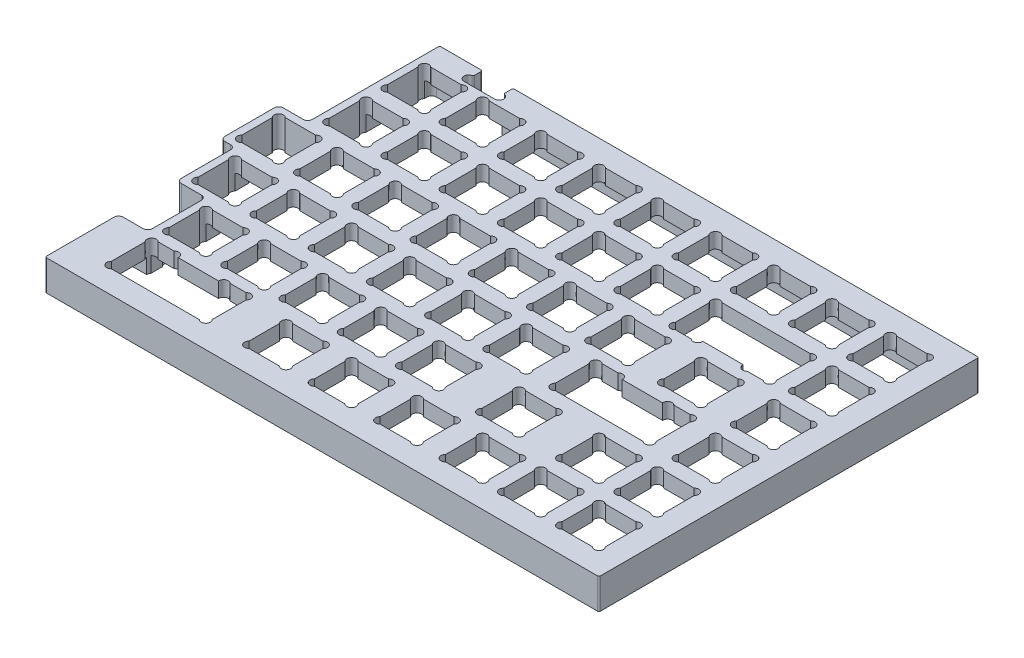
SolidWorks part; units mm, degrees
material "6061-T6 (SS)"
ref_plane "Front Plane" through (0, 0, 0) normal (0, 0, 1) x (1, 0, 0)
ref_plane "Top Plane" through (0, 0, 0) normal (0, 1, 0) x (1, 0, 0)
ref_plane "Right Plane" through (0, 0, 0) normal (1, 0, 0) x (0, 0, -1)
sketch "Sketch1" plane through (0, 0, 0) normal (0, 1, 0) x (1, 0, 0)
  line L0 (0, 0) -> (0, 124.3)
  line L1 (0, 124.3) -> (-176.45, 124.3)
  line L2 (-176.45, 124.3) -> (-176.45, 81.2)
  line L3 (-176.45, 81.2) -> (-185.975, 81.2)
  line L4 (-185.975, 81.2) -> (-185.975, 62.15)
  line L5 (-185.975, 62.15) -> (-181.2125, 62.15)
  line L6 (-181.2125, 62.15) -> (-181.2125, 43.1)
  line L7 (-181.2125, 43.1) -> (-171.6875, 43.1)
  line L8 (-171.6875, 43.1) -> (-171.6875, 24.05)
  line L9 (-171.6875, 24.05) -> (-181.2125, 24.05)
  line L10 (-181.2125, 24.05) -> (-181.2125, 0)
  line L11 (-181.2125, 0) -> (0, 0)
  dimension "D2" = 19.05
  dimension "D3" = 4.7625
  dimension "D4" = 9.525
  dimension "D6" = 176.45
  dimension "D7" = 9.525
  dimension "D5" = 43.1
  dimension "D1" = 24.05
extrude "Plate Frame" add sketch "Sketch1" along normal blind 5
sketch "Sketch2" plane through (0, 5, 0) normal (0, 1, 0) x (1, 0, 0)
  line L0 (-52.625, 14.525) -> (-33.575, 14.525) construction
  line L1 (-33.575, 14.525) -> (-14.525, 14.525) construction
  line L2 (-14.525, 14.525) -> (-14.525, 33.575) construction
  line L3 (-14.525, 33.575) -> (-14.525, 52.625) construction
  line L4 (-14.525, 52.625) -> (-14.525, 71.675) construction
  line L5 (-14.525, 71.675) -> (-14.525, 90.725) construction
  line L6 (-14.525, 90.725) -> (-14.525, 109.775) construction
  line L7 (-14.525, 109.775) -> (-33.575, 109.775) construction
  line L8 (-33.575, 109.775) -> (-52.625, 109.775) construction
  line L9 (-52.625, 109.775) -> (-71.675, 109.775) construction
  line L10 (-71.675, 109.775) -> (-90.725, 109.775) construction
  line L11 (-90.725, 109.775) -> (-109.775, 109.775) construction
  line L12 (-109.775, 109.775) -> (-128.825, 109.775) construction
  line L13 (-128.825, 109.775) -> (-147.875, 109.775) construction
  line L14 (-147.875, 109.775) -> (-166.925, 109.775) construction
  line L15 (-33.575, 33.575) -> (-14.525, 33.575) construction
  line L16 (-33.575, 33.575) -> (-33.575, 14.525) construction
  line L17 (-166.925, 90.725) -> (-147.875, 90.725) construction
  line L18 (-147.875, 90.725) -> (-128.825, 90.725) construction
  line L19 (-128.825, 90.725) -> (-109.775, 90.725) construction
  line L20 (-109.775, 90.725) -> (-90.725, 90.725) construction
  line L21 (-90.725, 90.725) -> (-71.675, 90.725) construction
  line L22 (-166.925, 90.725) -> (-166.925, 109.775) construction
  line L23 (-176.45, 124.3) -> (-176.45, 81.2) construction
  line L24 (-176.45, 71.675) -> (-157.4, 71.675) construction
  line L25 (-157.4, 71.675) -> (-138.35, 71.675) construction
  line L26 (-138.35, 71.675) -> (-119.3, 71.675) construction
  line L27 (-119.3, 71.675) -> (-100.25, 71.675) construction
  line L28 (-100.25, 71.675) -> (-81.2, 71.675) construction
  line L29 (-81.2, 71.675) -> (-62.15, 71.675) construction
  line L30 (-171.6875, 52.625) -> (-152.6375, 52.625) construction
  line L31 (-185.975, 81.2) -> (-185.975, 62.15) construction
  line L32 (-152.6375, 52.625) -> (-133.5875, 52.625) construction
  line L33 (-133.5875, 52.625) -> (-114.5375, 52.625) construction
  line L34 (-114.5375, 52.625) -> (-95.4875, 52.625) construction
  line L35 (-95.4875, 52.625) -> (-76.4375, 52.625) construction
  line L36 (-162.1625, 33.575) -> (-143.1125, 33.575) construction
  line L37 (-143.1125, 33.575) -> (-124.0625, 33.575) construction
  line L38 (-124.0625, 33.575) -> (-105.0125, 33.575) construction
  line L39 (-105.0125, 33.575) -> (-85.9625, 33.575) construction
  line L41 (-59.7687, 33.575) -> (-33.575, 33.575) construction
  line L42 (-52.625, 14.525) -> (-74.0562, 14.525) construction
  line L43 (-74.0562, 14.525) -> (-95.4875, 14.525) construction
  line L44 (-95.4875, 14.525) -> (-116.9187, 14.525) construction
  line L45 (-38.3375, 71.675) -> (-14.525, 71.675) construction
  point P0 (-14.525, 14.525)
  point P1 (-14.525, 33.575)
  point P2 (-14.525, 52.625)
  point P3 (-14.525, 71.675)
  point P4 (-14.525, 90.725)
  point P5 (-14.525, 109.775)
  point P6 (-33.575, 14.525)
  point P7 (-52.625, 14.525)
  point P8 (-33.575, 33.575)
  point P9 (-33.575, 109.775)
  point P10 (-52.625, 109.775)
  point P11 (-71.675, 109.775)
  point P12 (-90.725, 109.775)
  point P13 (-109.775, 109.775)
  point P14 (-128.825, 109.775)
  point P15 (-147.875, 109.775)
  point P16 (-166.925, 109.775)
  point P34 (-166.925, 90.725)
  point P35 (-147.875, 90.725)
  point P36 (-128.825, 90.725)
  point P37 (-109.775, 90.725)
  point P38 (-90.725, 90.725)
  point P39 (-71.675, 90.725)
  point P48 (-176.45, 71.675)
  point P49 (-157.4, 71.675)
  point P50 (-138.35, 71.675)
  point P51 (-119.3, 71.675)
  point P52 (-100.25, 71.675)
  point P53 (-81.2, 71.675)
  point P54 (-62.15, 71.675)
  point P62 (-152.6375, 52.625)
  point P65 (-185.975, 71.675)
  point P66 (-171.6875, 52.625)
  point P67 (-133.5875, 52.625)
  point P68 (-114.5375, 52.625)
  point P69 (-95.4875, 52.625)
  point P70 (-76.4375, 52.625)
  point P77 (-143.1125, 33.575)
  point P78 (-162.1625, 33.575)
  point P79 (-124.0625, 33.575)
  point P80 (-105.0125, 33.575)
  point P81 (-85.9625, 33.575)
  point P87 (-74.0562, 14.525)
  point P89 (-95.4875, 14.525)
  point P90 (-116.9187, 14.525)
  point P91 (-59.7687, 33.575)
  point P95 (-38.3375, 71.675)
  dimension "D1" = 19.05
  dimension "D2" = 9.525
  dimension "D3" = 9.525
  dimension "D4" = 4.7625
  dimension "D5" = 9.525
  dimension "D6" = 26.1938
  dimension "D7" = 21.4313
  dimension "D8" = 23.8125
sketch "Sketch3" plane through (0, 5, 0) normal (0, 1, 0) x (1, 0, 0)
  line L5 (-21.625, 19.5037) -> (-21.625, 9.5463)
  line L6 (-21.625, 21.625) -> (-7.425, 21.625) construction
  line L7 (-21.625, 21.625) -> (-21.625, 7.425) construction
  line L8 (-21.625, 7.425) -> (-7.425, 7.425) construction
  line L9 (-7.425, 21.625) -> (-7.425, 7.425) construction
  line L10 (-21.625, 21.625) -> (-7.425, 7.425) construction
  line L11 (-21.625, 7.425) -> (-7.425, 21.625) construction
  line L12 (-19.5037, 7.425) -> (-9.5463, 7.425)
  line L13 (-7.425, 19.5037) -> (-7.425, 9.5463)
  line L14 (-19.5037, 21.625) -> (-9.5463, 21.625)
  arc A4 (-21.625, 19.5037) -> (-19.5037, 21.625) centre (-20.5643, 20.5643) cw
  arc A5 (-7.425, 19.5037) -> (-9.5463, 21.625) centre (-8.4857, 20.5643) ccw
  arc A6 (-7.425, 9.5463) -> (-9.5463, 7.425) centre (-8.4857, 8.4857) cw
  arc A7 (-19.5037, 7.425) -> (-21.625, 9.5463) centre (-20.5643, 8.4857) cw
  point P13 (-14.525, 14.525)
  dimension "D1" = 1.5
  dimension "D2" = 14.2
extrude "1U" cut sketch "Sketch3" against normal through all
pattern_sketch "Sketch-Pattern1" of "1U" driven by "Sketch2"
sketch "Sketch5" plane through (0, 5, 0) normal (0, 1, 0) x (1, 0, 0)
  line L0 (-14.525, 90.725) -> (-43.1, 90.725) construction
  line L1 (-14.525, 52.625) -> (-45.4812, 52.625) construction
  line L2 (-116.9187, 14.525) -> (-152.6375, 14.525) construction
  point P0 (-43.1, 90.725)
  point P1 (-45.4812, 52.625)
  point P2 (-152.6375, 14.525)
  dimension "D1" = 28.575
  dimension "D2" = 30.9563
  dimension "D3" = 35.7188
sketch "Sketch4" plane through (0, 5, 0) normal (0, 1, 0) x (1, 0, 0)
  line L10 (-59.6, 97.775) -> (-51.95, 90.125) construction
  line L11 (-59.6, 82.475) -> (-50.15, 82.475) construction
  line L12 (-50.15, 83.675) -> (-36.05, 83.675) construction
  line L13 (-36.05, 82.475) -> (-26.6, 82.475) construction
  line L14 (-59.6, 82.475) -> (-51.95, 90.125) construction
  line L15 (-59.6, 97.775) -> (-26.6, 97.775) construction
  line L16 (-26.6, 97.775) -> (-26.6, 82.475) construction
  line L17 (-26.6, 97.775) -> (-34.25, 90.125) construction
  line L18 (-59.6, 82.475) -> (-59.6, 97.775) construction
  line L19 (-50.15, 83.675) -> (-50.15, 82.475) construction
  line L20 (-36.05, 83.675) -> (-36.05, 82.475) construction
  line L21 (-36.05, 83.675) -> (-50.15, 97.775) construction
  line L22 (-34.25, 90.125) -> (-26.6, 82.475) construction
  line L23 (-36.05, 82.475) -> (-31.325, 87.2) construction
  line L24 (-50.15, 82.475) -> (-54.875, 87.2) construction
  line L25 (-57.4787, 97.775) -> (-28.7213, 97.775)
  line L26 (-26.6, 95.6537) -> (-26.6, 84.5963)
  line L27 (-28.7213, 82.475) -> (-33.9287, 82.475)
  line L28 (-36.4829, 83.675) -> (-49.7171, 83.675)
  line L29 (-52.2713, 82.475) -> (-57.4787, 82.475)
  line L30 (-59.6, 84.5963) -> (-59.6, 95.6537)
  arc A6 (-59.6, 95.6537) -> (-57.4787, 97.775) centre (-58.5393, 96.7143) cw
  arc A7 (-26.6, 95.6537) -> (-28.7213, 97.775) centre (-27.6607, 96.7143) ccw
  arc A8 (-26.6, 84.5963) -> (-28.7213, 82.475) centre (-27.6607, 83.5357) cw
  arc A9 (-33.9287, 82.475) -> (-36.4829, 83.675) centre (-34.9893, 83.5357) cw
  arc A10 (-52.2713, 82.475) -> (-49.7171, 83.675) centre (-51.2107, 83.5357) ccw
  arc A11 (-57.4787, 82.475) -> (-59.6, 84.5963) centre (-58.5393, 83.5357) cw
  point P54 (-43.1, 90.725)
  dimension "D1" = 33
  dimension "D5" = 1.5
  dimension "D2" = 15.3
  dimension "D3" = 14.1
  dimension "D4" = 14.1
  dimension "D6" = 45
  dimension "D7" = 45
sketch "Sketch6" plane through (0, 5, 0) normal (0, 1, 0) x (1, 0, 0)
  line L27 (-169.1375, 22.775) -> (-159.6875, 22.775) construction
  line L28 (-159.6875, 22.775) -> (-159.6875, 21.575) construction
  line L29 (-159.6875, 21.575) -> (-145.5875, 21.575) construction
  line L30 (-145.5875, 21.575) -> (-145.5875, 22.775) construction
  line L31 (-145.5875, 22.775) -> (-136.1375, 22.775) construction
  line L32 (-136.1375, 22.775) -> (-136.1375, 7.475) construction
  line L33 (-136.1375, 7.475) -> (-169.1375, 7.475) construction
  line L34 (-169.1375, 7.475) -> (-169.1375, 22.775) construction
  line L35 (-159.6875, 21.575) -> (-145.5875, 7.475) construction
  line L36 (-169.1375, 7.475) -> (-161.4875, 15.125) construction
  line L37 (-161.4875, 15.125) -> (-169.1375, 22.775) construction
  line L38 (-136.1375, 7.475) -> (-143.7875, 15.125) construction
  line L39 (-143.7875, 15.125) -> (-136.1375, 22.775) construction
  line L40 (-145.5875, 22.775) -> (-140.8625, 18.05) construction
  line L41 (-159.6875, 22.775) -> (-164.4125, 18.05) construction
  line L42 (-169.1375, 20.6537) -> (-169.1375, 9.5963)
  line L43 (-167.0162, 7.475) -> (-138.2588, 7.475)
  line L44 (-136.1375, 9.5963) -> (-136.1375, 20.6537)
  line L45 (-138.2588, 22.775) -> (-143.4662, 22.775)
  line L46 (-146.0204, 21.575) -> (-159.2546, 21.575)
  line L47 (-161.8088, 22.775) -> (-167.0162, 22.775)
  line L48 (-61.9812, 60.875) -> (-52.5312, 60.875) construction
  line L49 (-52.5312, 60.875) -> (-52.5312, 59.675) construction
  line L50 (-52.5312, 59.675) -> (-38.4312, 59.675) construction
  line L51 (-38.4312, 59.675) -> (-38.4312, 60.875) construction
  line L52 (-38.4312, 60.875) -> (-28.9812, 60.875) construction
  line L53 (-28.9812, 60.875) -> (-28.9812, 45.575) construction
  line L54 (-28.9812, 45.575) -> (-61.9812, 45.575) construction
  line L55 (-61.9812, 45.575) -> (-61.9812, 60.875) construction
  line L56 (-52.5312, 59.675) -> (-38.4312, 45.575) construction
  line L57 (-61.9812, 45.575) -> (-54.3312, 53.225) construction
  line L58 (-54.3312, 53.225) -> (-61.9812, 60.875) construction
  line L59 (-28.9812, 45.575) -> (-36.6313, 53.225) construction
  line L60 (-36.6313, 53.225) -> (-28.9812, 60.875) construction
  line L61 (-38.4312, 60.875) -> (-33.7062, 56.15) construction
  line L62 (-52.5312, 60.875) -> (-57.2562, 56.15) construction
  line L63 (-61.9812, 58.7537) -> (-61.9812, 47.6963)
  line L64 (-59.8599, 45.575) -> (-31.1026, 45.575)
  line L65 (-28.9812, 47.6963) -> (-28.9812, 58.7537)
  line L66 (-31.1026, 60.875) -> (-36.3099, 60.875)
  line L67 (-38.8641, 59.675) -> (-52.0984, 59.675)
  line L68 (-54.6526, 60.875) -> (-59.8599, 60.875)
  arc A19 (-169.1375, 20.6537) -> (-167.0162, 22.775) centre (-168.0768, 21.7143) cw
  arc A20 (-161.8088, 22.775) -> (-159.2546, 21.575) centre (-160.7482, 21.7143) cw
  arc A21 (-143.4662, 22.775) -> (-146.0204, 21.575) centre (-144.5268, 21.7143) ccw
  arc A22 (-138.2588, 22.775) -> (-136.1375, 20.6537) centre (-137.1982, 21.7143) cw
  arc A23 (-136.1375, 9.5963) -> (-138.2588, 7.475) centre (-137.1982, 8.5357) cw
  arc A24 (-167.0162, 7.475) -> (-169.1375, 9.5963) centre (-168.0768, 8.5357) cw
  arc A25 (-61.9812, 58.7537) -> (-59.8599, 60.875) centre (-60.9206, 59.8143) cw
  arc A26 (-54.6526, 60.875) -> (-52.0984, 59.675) centre (-53.5919, 59.8143) cw
  arc A27 (-36.3099, 60.875) -> (-38.8641, 59.675) centre (-37.3706, 59.8143) ccw
  arc A28 (-31.1026, 60.875) -> (-28.9812, 58.7537) centre (-30.0419, 59.8143) cw
  arc A29 (-28.9812, 47.6963) -> (-31.1026, 45.575) centre (-30.0419, 46.6357) cw
  arc A30 (-59.8599, 45.575) -> (-61.9812, 47.6963) centre (-60.9206, 46.6357) cw
  point P56 (-152.6375, 14.525)
  point P88 (-45.4812, 52.625)
  dimension "D18" = 1.5
  dimension "D25" = 1.5
  dimension "D12" = 33
  dimension "D13" = 14.1
  dimension "D14" = 14.1
  dimension "D15" = 15.3
  dimension "D16" = 45
  dimension "D17" = 45
  dimension "D19" = 33
  dimension "D20" = 14.1
  dimension "D21" = 14.1
  dimension "D22" = 15.3
  dimension "D23" = 45
  dimension "D24" = 45
extrude "2U-Backspace" cut sketch "Sketch4" against normal through all
extrude "EnterAndSpace" cut sketch "Sketch6" against normal through all
sketch "Sketch8" plane through (0, 0, 0) normal (0, -1, 0) x (1, 0, 0)
  line L0 (-181.2125, 0) -> (0, 0)
  line L1 (0, 0) -> (0, -124.3)
  line L2 (0, -124.3) -> (-176.45, -124.3)
  line L3 (-176.45, -124.3) -> (-176.45, -81.2)
  line L4 (-176.45, -81.2) -> (-185.975, -81.2)
  line L5 (-185.975, -81.2) -> (-185.975, -62.15)
  line L6 (-185.975, -62.15) -> (-181.2125, -62.15)
  line L7 (-181.2125, -62.15) -> (-181.2125, -43.1)
  line L8 (-181.2125, -43.1) -> (-171.6875, -43.1)
  line L9 (-171.6875, -43.1) -> (-171.6875, -24.05)
  line L10 (-171.6875, -24.05) -> (-181.2125, -24.05)
  line L11 (-181.2125, -24.05) -> (-181.2125, 0)
  line L12 (-178.7875, -5) -> (-5, -5)
  line L13 (-5, -5) -> (-5, -119.3)
  line L14 (-5, -119.3) -> (-174.025, -119.3)
  line L15 (-174.025, -119.3) -> (-174.025, -78.775)
  line L16 (-171.4713, -78.775) -> (-181.4287, -78.775) construction
  line L17 (-174.025, -78.775) -> (-183.55, -78.775)
  line L18 (-183.55, -78.775) -> (-183.55, -64.575)
  line L19 (-183.55, -64.575) -> (-178.7875, -64.575)
  line L20 (-178.7875, -64.575) -> (-178.7875, -45.525)
  line L21 (-178.7875, -45.525) -> (-169.2625, -45.525)
  line L22 (-169.2625, -45.525) -> (-169.2625, -21.575)
  line L23 (-169.2625, -21.575) -> (-178.7875, -21.575)
  line L24 (-178.7875, -21.575) -> (-178.7875, -5)
  line L25 (-169.2625, -38.5537) -> (-169.2625, -28.5963) construction
  line L27 (-176.6662, -45.525) -> (-166.7088, -45.525) construction
  line L28 (-178.7875, -57.6037) -> (-178.7875, -47.6463) construction
  line L29 (-181.4287, -64.575) -> (-171.4713, -64.575) construction
  line L30 (-183.55, -76.6537) -> (-183.55, -66.6963) construction
  line L31 (-174.025, -95.7037) -> (-174.025, -85.7463) construction
  line L32 (-146.0204, -21.575) -> (-159.2546, -21.575) construction
  line L33 (-171.6875, -24.05) -> (-169.2625, -24.05) construction
  line L34 (-178.7875, -21.575) -> (-181.2125, -21.575) construction
  dimension "D2" = 5
  dimension "D3" = 5
  dimension "D4" = 5
extrude "Lip" add sketch "Sketch8" along normal blind 5
sketch "Sketch11" plane through (0, 5, 0) normal (0, 1, 0) x (1, 0, 0)
  line L0 (-162.425, 124.3) -> (-152.425, 124.3) construction
  line L1 (0, 124.3) -> (-176.45, 124.3) construction
  line L2 (-152.425, 124.3) -> (-152.425, 118.275) construction
  line L3 (-152.425, 118.275) -> (-162.425, 118.275) construction
  line L4 (-162.425, 118.275) -> (-162.425, 124.3) construction
  line L5 (-147.875, 109.775) -> (-166.925, 109.775) construction
  line L7 (-157.425, 124.3) -> (-157.425, 118.275) construction
  line L8 (-166.925, 90.725) -> (-166.925, 109.775) construction
  line L9 (-162.425, 121.275) -> (-162.425, 124.3)
  line L10 (-162.425, 124.3) -> (-152.425, 124.3)
  line L11 (-152.425, 124.3) -> (-152.425, 121.275)
  line L12 (-152.425, 118.275) -> (-162.425, 118.275)
  arc A0 (-162.425, 118.275) -> (-162.425, 121.275) centre (-162.425, 119.775) cw
  arc A1 (-152.425, 118.275) -> (-152.425, 121.275) centre (-152.425, 119.775) ccw
  dimension "D5" = 1.5
  dimension "D1" = 10
  dimension "D2" = 8.5
  dimension "D3" = 9.5
extrude "USB-Slot" cut sketch "Sketch11" against normal through all
sketch "Sketch12" plane through (0, -5, 0) normal (0, -1, 0) x (1, 0, 0)
  line L0 (-178.7125, -2.5) -> (-90.6063, -2.5) construction
  line L1 (-90.6063, -2.5) -> (-2.5, -2.5) construction
  line L2 (-2.5, -2.5) -> (-2.5, -62.15) construction
  line L3 (-2.5, -62.15) -> (-2.5, -121.8) construction
  line L4 (-2.5, -121.8) -> (-88.225, -121.8) construction
  line L5 (-88.225, -121.8) -> (-173.95, -121.8) construction
  line L6 (0, 0) -> (-181.2125, 0) construction
  line L7 (-181.2125, 0) -> (-181.2125, -24.05) construction
  line L8 (0, -124.3) -> (0, 0) construction
  line L10 (-176.45, -81.2) -> (-176.45, -124.3) construction
  line L11 (-152.425, -124.3) -> (0, -124.3) construction
  point P0 (-178.7125, -2.5)
  point P1 (-90.6063, -2.5)
  point P2 (-2.5, -2.5)
  point P3 (-2.5, -121.8)
  point P4 (-88.225, -121.8)
  point P5 (-173.95, -121.8)
  point P8 (-2.5, -62.15)
  point P24 (-90.6063, -2.5)
  dimension "D1" = 2.5
  dimension "D2" = 2.5
  dimension "D3" = 2.5
  dimension "D4" = 2.5
  dimension "D5" = 2.5
sketch "Sketch10" plane through (0, 0, 0) normal (0, 1, 0) x (1, 0, 0)
  circle A0 centre (-172.9643, 115.8143) radius 1.5
  circle A1 centre (-172.9643, 103.7357) radius 1.5
  circle A2 centre (-172.9643, 96.7643) radius 1.5
  circle A3 centre (-172.9643, 84.6857) radius 1.5
  circle A4 centre (-182.4893, 77.7143) radius 1.5
  circle A5 centre (-182.4893, 65.6357) radius 1.5
  circle A6 centre (-177.7268, 58.6643) radius 1.5
  circle A7 centre (-177.7268, 46.5857) radius 1.5
  circle A8 centre (-168.2018, 39.6143) radius 1.5
  circle A9 centre (-168.2018, 27.5357) radius 1.5
  arc A10 (-171.9037, 116.875) -> (-174.025, 114.7537) centre (-172.9643, 115.8143) ccw construction
  circle A11 centre (-168.0768, 21.7143) radius 1.5
extrude "Cut-Extrude1" cut sketch "Sketch10" against normal through all
fillet "Fillet2" radius 1.5 13 edges at (-5, -2.5, -5) (-5, -2.5, -119.3) (-174.025, -2.5, -119.3) (-178.7875, -2.5, -21.575) (-181.2125, 0, -62.15) (-171.6875, 0, -43.1) (-181.2125, 0, -24.05) (-171.6875, 0, -24.05) (-181.2125, 0, -43.1) (-185.975, 0, -62.15) (-185.975, 0, -81.2) (-176.45, 0, -81.2) (-178.7875, -2.5, -5)
fillet "Fillet3" radius 0.5 11 edges at (-169.2625, -2.5, -45.525) (-178.7875, -2.5, -64.575) (-174.025, -2.5, -78.775) (-152.425, 0, -121.275) (-162.425, 0, -124.3) (-152.425, 0, -124.3) (-162.425, 0, -121.275) (-181.2125, 0, 0) (-176.45, 0, -124.3) (0, 0, -124.3) (0, 0, 0)
hole_wizard "M2x0.4 Tapped Hole1" positions "Sketch13" profile "Sketch14" tap size "M2x0.4" standard "ANSI Metric"
sketch "Sketch13" plane through (0, -5, 0) normal (0, -1, 0) x (-1, 0, 0)
  point P0 (173.95, 121.8)
  point P3 (88.225, 121.8)
  point P6 (2.5, 121.8)
  point P9 (2.5, 62.15)
  point P12 (2.5, 2.5)
  point P15 (90.6063, 2.5)
  point P18 (178.7125, 2.5)
sketch "Sketch14" plane through (-173.95, -5, -121.8) normal (1, 0, 0) x (0, 0, -1)
  line L0 (0, 0) -> (0, 5.6807)
  line L1 (0, 5.6807) -> (0.8, 5.2)
  line L2 (0.8, 5.2) -> (0.8, 0)
  line L5 (0.8, 0) -> (0, 0)
  line L10 (0, 5.6807) -> (-0.8, 5.2) construction
  line L11 (0, -6.35) -> (0, 107.95) construction
  dimension "Tap Drill Dia." = 1.6
  dimension "Tap Drill Depth" = 5.2
  dimension "Drill Angle" = 118
cosmetic thread "Hole Thread1" parameters "D1"=4, "D2"=2
cosmetic thread "Hole Thread2" parameters "D1"=4, "D2"=2
cosmetic thread "Hole Thread3" parameters "D1"=4, "D2"=2
cosmetic thread "Hole Thread4" parameters "D1"=4, "D2"=2
cosmetic thread "Hole Thread5" parameters "D1"=4, "D2"=2
cosmetic thread "Hole Thread6" parameters "D1"=4, "D2"=2
cosmetic thread "Hole Thread7" parameters "D1"=4, "D2"=2
equation "\"D3@Sketch1\"=19.05/4"
equation "\"D2@Sketch2\"=19.05/2"
equation "\"D3@Sketch2\"=19.05/2"
equation "\"D4@Sketch2\"=19.05/4"
equation "\"D4@Sketch1\"=19.05/2"
equation "\"D5@Sketch2\"=19.05/2"
equation "\"D6@Sketch2\"=19.05 + 19.05*.75/2"
equation "\"D7@Sketch2\"=19.05/2 + 19.05*1.25/2"
equation "\"D8@Sketch2\"=19.05/2 + 19.05*1.5/2"
equation "\"D1@Sketch5\"=19.05*2/2 + 19.05/2"
equation "\"D2@Sketch5\"=19.05*2.25/2 + 19.05/2"
equation "\"D3@Sketch5\"=19.05*2.75/2 + 19.05/2"
equation "\"D5@Sketch1\"=2*19.05 + 5"
equation "\"D1@Sketch1\"=19.05 + 5"
equation "\"D6@Sketch1\"=19.05*9 + 5"
